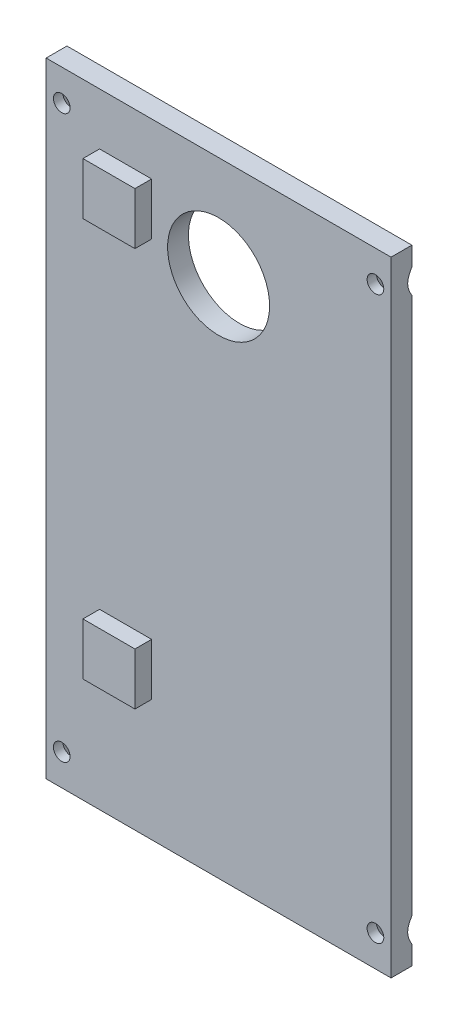
SolidWorks part; units mm, degrees
ref_plane "Front Plane" through (0, 0, 0) normal (0, 0, 1) x (1, 0, 0)
ref_plane "Top Plane" through (0, 0, 0) normal (0, 1, 0) x (1, 0, 0)
ref_plane "Right Plane" through (0, 0, 0) normal (1, 0, 0) x (0, 0, -1)
sketch "Sketch1" plane through (0, 0, 0) normal (0, 0, 1) x (1, 0, 0)
  line L0 (0, 0) -> (0, 30) construction
  line L1 (-16.575, -30) -> (16.575, -30)
  line L2 (-16.575, -30) -> (-16.575, 30)
  line L3 (-16.575, 30) -> (16.575, 30)
  line L4 (16.575, -30) -> (16.575, 30)
  line L5 (-16.575, -30) -> (16.575, 30) construction
  line L6 (-16.575, 30) -> (16.575, -30) construction
  line L7 (0, 25) -> (11.44, 25) construction
  line L8 (11.44, 25) -> (11.44, -18.32) construction
  circle A0 centre (0, 20.1) radius 4.9
  point P0 (0, 0)
  dimension "D3" = 9.8
  dimension "D1" = 33.15
  dimension "D2" = 60
  dimension "D4" = 11.44
  dimension "D5" = 43.32
extrude "Boss-Extrude1" add sketch "Sketch1" along normal blind 2
sketch "Sketch3" plane through (0, 0, 2) normal (0, 0, 1) x (1, 0, 0)
  line L0 (0, 25) -> (-11.44, 25) construction
  line L1 (-11.44, 25) -> (-11.44, -18.32) construction
  line L3 (-11.44, 25) -> (-6.44, 25)
  line L4 (-11.44, 25) -> (-11.44, 20)
  line L5 (-11.44, 20) -> (-6.44, 20)
  line L6 (-6.44, 25) -> (-6.44, 20)
  line L7 (-11.44, -18.32) -> (-6.44, -18.32)
  line L8 (-11.44, -18.32) -> (-11.44, -13.32)
  line L9 (-11.44, -13.32) -> (-6.44, -13.32)
  line L10 (-6.44, -18.32) -> (-6.44, -13.32)
  circle A0 centre (0, 20.1) radius 4.9 construction
  dimension "D1" = 11.44
  dimension "D2" = 43.32
  dimension "D3" = 5
  dimension "D4" = 5
  dimension "D5" = 5
  dimension "D6" = 5
extrude "Boss-Extrude2" add sketch "Sketch3" along normal blind 1.6
sketch "Sketch4" plane through (0, 0, 0) normal (0, 0, -1) x (-1, 0, 0)
  line L0 (-16.575, 30) -> (16.575, 30) construction
  line L1 (-16.575, -30) -> (-16.575, 30) construction
  line L2 (0, 0) -> (0, 18.7662) construction
  line L3 (0, 0) -> (24.504, 0) construction
  circle A0 centre (-15.075, 27) radius 0.8
  circle A1 centre (15.075, 27) radius 0.8
  circle A2 centre (15.075, -27) radius 0.8
  circle A3 centre (-15.075, -27) radius 0.8
  dimension "D3" = 1.6
  dimension "D1" = 3
  dimension "D2" = 1.5
extrude "Cut-Extrude1" cut sketch "Sketch4" against normal up to surface (2 mm away) up to face at (-8.94, 22.5, 2)
chamfer "Chamfer1" distance 1.1 angle 45 4 edges at (-15.875, -27, 0) (15.875, -27, 0) (-14.275, 27, 0) (14.275, 27, 0)
